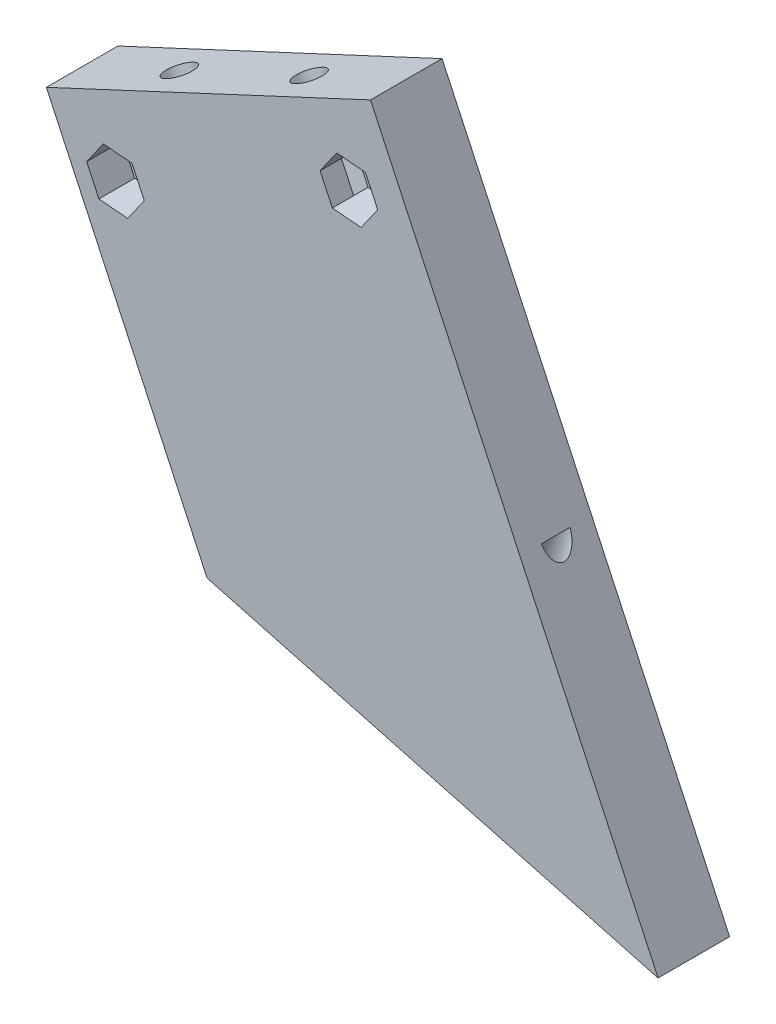
SolidWorks part; units mm, degrees
material "ABS"
ref_plane "Front Plane" through (0, 0, 0) normal (0, 0, 1) x (1, 0, 0)
ref_plane "Top Plane" through (0, 0, 0) normal (0, 1, 0) x (1, 0, 0)
ref_plane "Right Plane" through (0, 0, 0) normal (1, 0, 0) x (0, 0, -1)
sketch "Sketch1" plane through (0, 0, 0) normal (0, 0, 1) x (1, 0, 0)
  line L0 (127.3464, -36.4832) -> (87.1479, 49.7228)
  line L1 (198.5484, -55.5617) -> (44.0003, -14.1506) construction
  line L2 (87.1479, 49.7228) -> (41.8325, 28.5919)
  line L3 (41.8325, 28.5919) -> (64.3001, -19.59)
  line L4 (64.3001, -19.59) -> (127.3464, -36.4832)
  line L6 (189.2372, 97.3278) -> (-129.7831, -51.4338) construction
  line L7 (127.3464, -36.4832) -> (87.1479, 49.7228) construction
  dimension "D1" = 50
extrude "Boss-Extrude1" add sketch "Sketch1" against normal blind 10
sketch "Sketch2" plane through (-3.4798, 7.4624, 0) normal (-0.4226, 0.9063, 0) x (0.9063, 0.4226, 0)
  line L0 (49.9966, 5) -> (99.9966, 5) construction
  line L1 (49.9966, 10) -> (49.9966, 0) construction
  line L2 (99.9966, 10) -> (99.9966, 0) construction
  line L3 (74.9966, 10) -> (74.9966, 0) construction
  line L4 (84.9966, 0.9585) -> (88.4966, 2.9793)
  line L5 (88.4966, 2.9793) -> (88.4966, 7.0207)
  line L6 (88.4966, 7.0207) -> (84.9966, 9.0415)
  line L7 (84.9966, 9.0415) -> (81.4966, 7.0207)
  line L8 (81.4966, 7.0207) -> (81.4966, 2.9793)
  line L9 (81.4966, 2.9793) -> (84.9966, 0.9585)
  line L10 (99.9966, 10) -> (49.9966, 10) construction
  line L11 (99.9966, 0) -> (49.9966, 0) construction
  line L12 (68.4966, 2.9793) -> (64.9966, 0.9585)
  line L13 (64.9966, 0.9585) -> (61.4966, 2.9793)
  line L14 (68.4966, 7.0207) -> (68.4966, 2.9793)
  line L15 (64.9966, 9.0415) -> (68.4966, 7.0207)
  line L16 (61.4966, 7.0207) -> (64.9966, 9.0415)
  line L17 (61.4966, 2.9793) -> (61.4966, 7.0207)
  circle A0 centre (84.9966, 5) radius 3.5 construction
  circle A1 centre (84.9966, 5) radius 2
  circle A2 centre (64.9966, 5) radius 3.5 construction
  circle A3 centre (64.9966, 5) radius 2
  dimension "D3" = 4
  dimension "D1" = 15
  dimension "D2" = 7
extrude "Cut-Extrude1" cut sketch "Sketch2" against normal through all contours A3 | A1 region at (73.5533, 43.3835, -5) region at (55.4272, 34.9312, -5)
extrude "Cut-Extrude2" cut sketch "Sketch2<3>" against normal through all from offset 4 offset against normal yes
sketch "Sketch2<3>" plane through (-3.4798, 7.4624, 0) normal (-0.4226, 0.9063, 0) x (0.9063, 0.4226, 0) same geometry as "Sketch2"
sketch "Sketch3" plane through (-0.5902, -2.2027, 0) normal (-0.2588, -0.9659, 0) x (0.9659, -0.2588, 0)
  line L0 (132.4498, -5) -> (67.1794, -5) construction
  line L1 (132.4498, -10) -> (132.4498, 0) construction
  line L2 (67.1794, -10) -> (67.1794, 0) construction
  circle A0 centre (82.8091, -5) radius 2
  circle A1 centre (102.8936, -5) radius 2
  circle A2 centre (102.8936, -5) radius 1.5 construction
  circle A3 centre (82.8091, -5) radius 1.5 construction
  dimension "D1" = 4
  dimension "D2" = 4
extrude "Cut-Extrude3" cut sketch "Sketch3" against normal blind 35
sketch "Sketch4" plane through (0, 0, 0) normal (0, 0, 1) x (1, 0, 0)
  line L0 (127.3464, -36.4832) -> (87.1479, 49.7228) construction
  line L1 (88.1497, 36.9265) -> (86.4417, 40.5893)
  line L2 (86.4417, 40.5893) -> (82.4157, 40.9416)
  line L3 (82.4157, 40.9416) -> (80.0976, 37.631)
  line L4 (80.0976, 37.631) -> (81.8056, 33.9682)
  line L5 (81.8056, 33.9682) -> (85.8317, 33.616)
  line L6 (85.8317, 33.616) -> (88.1497, 36.9265)
  line L7 (87.1479, 49.7228) -> (41.8325, 28.5919) construction
  line L8 (55.5227, 21.7123) -> (53.8147, 25.3751)
  line L9 (53.8147, 25.3751) -> (49.7886, 25.7273)
  line L10 (49.7886, 25.7273) -> (47.4705, 22.4167)
  line L11 (47.4705, 22.4167) -> (49.1785, 18.7539)
  line L12 (49.1785, 18.7539) -> (53.2046, 18.4017)
  line L13 (53.2046, 18.4017) -> (55.5227, 21.7123)
  line L14 (87.1479, 49.7228) -> (41.8325, 28.5919) construction
  line L15 (41.8325, 28.5919) -> (64.3001, -19.59) construction
  circle A0 centre (84.1237, 37.2788) radius 2
  circle A1 centre (84.1237, 37.2788) radius 3.5 construction
  circle A2 centre (51.4966, 22.0645) radius 2
  circle A3 centre (51.4966, 22.0645) radius 3.5 construction
  dimension "D4" = 4
  dimension "D7" = 4
  dimension "D1" = 8
  dimension "D2" = 10
  dimension "D3" = 7
  dimension "D5" = 0
  dimension "D6" = 7
  dimension "D8" = 10
  dimension "D9" = 6
extrude "Cut-Extrude4" cut sketch "Sketch4" against normal blind 10 contours A0 | A2 region at (84.1237, 37.2788, 0) region at (51.4966, 22.0645, 0)
extrude "Cut-Extrude5" cut sketch "Sketch4<3>" against normal blind 5 from surface starting at face at (86.1237, 37.2788, 0)
sketch "Sketch4<3>" plane through (0, 0, 0) normal (0, 0, 1) x (1, 0, 0) same geometry as "Sketch4"
